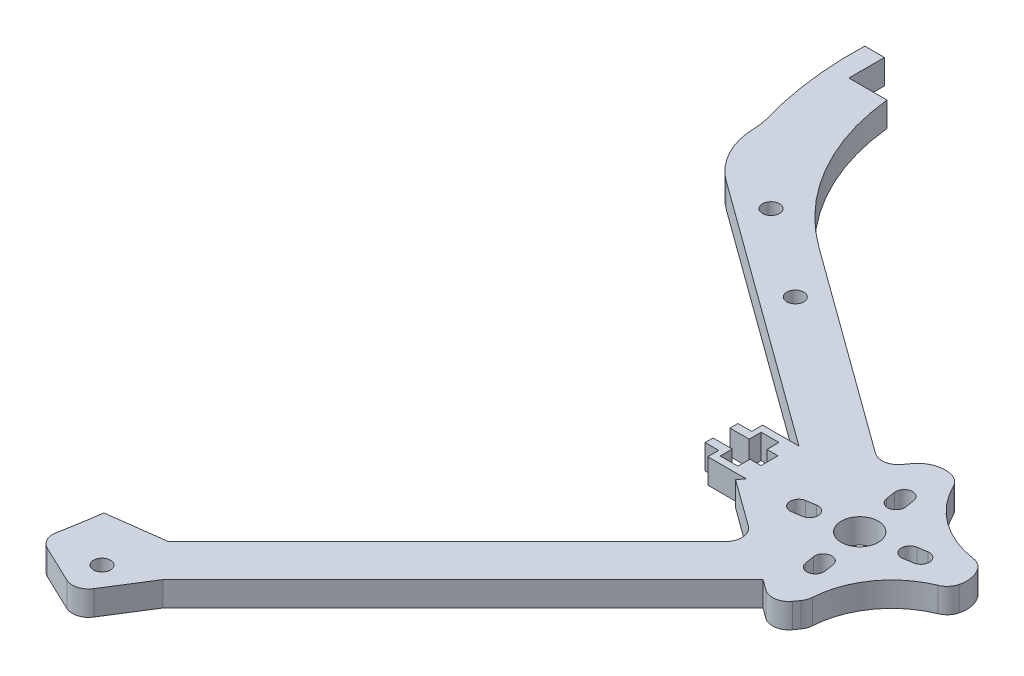
SolidWorks part; units mm, degrees
material "PPS"
ref_plane "前视基准面" through (0, 0, 0) normal (0, 0, 1) x (1, 0, 0)
ref_plane "上视基准面" through (0, 0, 0) normal (0, 1, 0) x (1, 0, 0)
ref_plane "右视基准面" through (0, 0, 0) normal (1, 0, 0) x (0, 0, -1)
sketch "草图3" plane through (0, 0, 0) normal (0, 1, 0) x (1, 0, 0)
  line L0 (0, 0) -> (35.4735, 0) construction
  line L1 (0, 0) -> (62.3757, -45.3186) construction
  line L2 (41.1319, -24.0128) -> (94.6944, -62.9282)
  line L3 (94.6944, -62.9282) -> (100.1314, -55.4448)
  line L4 (100.1314, -55.4448) -> (122.7839, -71.9028)
  line L5 (122.7839, -71.9028) -> (106.3259, -94.5552)
  line L6 (83.6734, -78.0972) -> (106.3259, -94.5552) construction
  line L9 (77.9994, -109.7251) -> (128.6275, -40.0415) construction
  line L11 (103.2286, -75) -> (90.242, -77.0569) construction
  line L13 (111.1302, -73.7485) -> (112.8586, -73.4748) construction
  line L14 (110.8877, -72.2176) -> (112.6161, -71.9438)
  line L15 (111.3726, -75.2794) -> (113.1011, -75.0057)
  line L16 (101.9772, -67.0985) -> (101.7034, -65.37) construction
  line L17 (103.5081, -66.856) -> (103.2343, -65.1276)
  line L18 (100.4463, -67.341) -> (100.1725, -65.6125)
  line L19 (95.3271, -76.2515) -> (93.5987, -76.5252) construction
  line L20 (95.5696, -77.7824) -> (93.8412, -78.0562)
  line L21 (95.0847, -74.7206) -> (93.3562, -74.9943)
  line L22 (104.4801, -82.9015) -> (104.7539, -84.63) construction
  line L23 (102.9492, -83.144) -> (103.223, -84.8724)
  line L24 (106.011, -82.659) -> (106.2848, -84.3875)
  line L25 (35.5479, -31.6984) -> (84.1364, -67)
  line L26 (84.1364, -67) -> (77.5, -67)
  line L27 (77.5, -67) -> (77.5, -69)
  line L28 (77.5, -69) -> (75, -69)
  line L29 (75, -69) -> (75, -70.45)
  line L30 (75, -70.45) -> (78.5, -70.45)
  line L31 (78.5, -70.45) -> (78.5, -68.25)
  line L32 (78.5, -68.25) -> (81.75, -68.25)
  line L33 (81.75, -68.25) -> (81.75, -70.45)
  line L34 (81.75, -70.45) -> (83.75, -70.45)
  line L35 (83.75, -70.45) -> (83.75, -73.55)
  line L36 (68.8077, -72) -> (90.242, -72) construction
  line L37 (81.75, -73.55) -> (83.75, -73.55)
  line L38 (81.75, -75.75) -> (81.75, -73.55)
  line L39 (78.5, -75.75) -> (81.75, -75.75)
  line L40 (78.5, -73.55) -> (78.5, -75.75)
  line L41 (75, -73.55) -> (78.5, -73.55)
  line L42 (75, -75) -> (75, -73.55)
  line L43 (77.5, -75) -> (75, -75)
  line L44 (77.5, -77) -> (77.5, -75)
  line L45 (84.1364, -77) -> (77.5, -77)
  line L47 (83.6734, -78.0972) -> (84.4706, -77)
  line L48 (84.4706, -77) -> (84.1364, -77)
  line L51 (41.6712, -139.6547) -> (94.9997, -86.3262)
  line L52 (94.9997, -86.3262) -> (83.6734, -78.0972)
  line L58 (47.1809, -146.1658) -> (101.962, -91.3847)
  line L61 (101.962, -91.3847) -> (106.3259, -94.5552)
  line L63 (31.6811, -151.7709) -> (40.8875, -156.1591)
  line L64 (47.1809, -146.1658) -> (40.8875, -156.1591)
  line L65 (41.6712, -139.6547) -> (31.2614, -141.0241)
  line L66 (42.309, -153.902) -> (47.6512, -145.4189) construction
  line L67 (31.6811, -151.7709) -> (38.4796, -155.0114) construction
  circle A5 centre (103.2286, -75) radius 3.375
  arc A6 (110.8877, -72.2176) -> (111.3726, -75.2794) centre (111.1302, -73.7485) ccw
  arc A7 (113.1011, -75.0057) -> (112.6161, -71.9438) centre (112.8586, -73.4748) ccw
  arc A8 (103.5081, -66.856) -> (100.4463, -67.341) centre (101.9772, -67.0985) cw
  arc A9 (100.1725, -65.6125) -> (103.2343, -65.1276) centre (101.7034, -65.37) cw
  arc A10 (95.5696, -77.7824) -> (95.0847, -74.7206) centre (95.3271, -76.2515) ccw
  arc A11 (93.3562, -74.9943) -> (93.8412, -78.0562) centre (93.5987, -76.5252) ccw
  arc A12 (102.9492, -83.144) -> (106.011, -82.659) centre (104.4801, -82.9015) cw
  arc A13 (106.2848, -84.3875) -> (103.223, -84.8724) centre (104.7539, -84.63) cw
  arc A16 (41.1319, -24.0128) -> (35.5479, -31.6984) centre (38.3399, -27.8556) ccw
  circle A17 centre (103.2286, -75) radius 66.25 construction
  circle A18 centre (44.0442, -32) radius 1.55
  circle A19 centre (60.2246, -43.7557) radius 1.55
  circle A28 centre (39.335, -149.4323) radius 1.55
  arc A29 (30.0249, -148.5011) -> (31.2329, -97.7907) centre (-122.0773, -119.5082) ccw construction
  arc A33 (31.2614, -141.0241) -> (30.0249, -148.5011) centre (-122.0773, -119.5082) cw
  arc A34 (30.0249, -148.5011) -> (31.6811, -151.7709) centre (32.9719, -149.0628) ccw construction
  arc A35 (30.0249, -148.5011) -> (31.6811, -151.7709) centre (32.9719, -149.0628) ccw
  point P11 (114.5549, -83.229)
  point P20 (111.9944, -73.6116)
  point P27 (101.8403, -66.2343)
  point P35 (94.4629, -76.3884)
  point P42 (104.617, -83.7657)
  point P54 (94.9997, -86.3262)
  point P67 (83.75, -72)
  dimension "D2" = 45
  dimension "D3" = 6.75
  dimension "D4" = 1.55
  dimension "D7" = 14
  dimension "D11" = 132.5
  dimension "D12" = 3.1
  dimension "D26" = 8.5
  dimension "D27" = 3.1
  dimension "D1" = 36
  dimension "D5" = 1.75
  dimension "D6" = 8
  dimension "D8" = 14
  dimension "D9" = 4.75
  dimension "D10" = 75
  dimension "D13" = 32
  dimension "D14" = 20
  dimension "D15" = 7.5
  dimension "D16" = 10
  dimension "D17" = 3.1
  dimension "D18" = 3.5
  dimension "D19" = 3.25
  dimension "D20" = 2
  dimension "D21" = 2.5
  dimension "D22" = 72
  dimension "D23" = 75
  dimension "D24" = 1.45
  dimension "D25" = 45
extrude "凸台-拉伸1" add sketch "草图3" along normal blind 4.5 contours L5 L4 L3 L2 A16 L25 L26 L27 L28 L29 L30 L31 L32 L33 L34 L35 L37 L38 L39 L40 L41 L42 L43 L44 L45 L48 L47 L52 L51 A19 A18 A11 L21 A10 L20 A7 L15 A6 L14 region at (66.9596, 0, 44.7829)
fillet "圆角-美观1" radius 5 2 edges at (100.1314, 2.25, 55.4448) (122.7839, 2.25, 71.9028)
sketch "草图4" plane through (0, 4.5, 0) normal (0, 1, 0) x (1, 0, 0)
  line L0 (104.1765, -58.3837) -> (118.7388, -68.9638)
  line L1 (119.8449, -75.9478) -> (109.2648, -90.5101)
  line L3 (103.2286, -75) -> (124.6569, -90.5685) construction
  line L4 (103.2286, -75) -> (89.033, -94.5387) construction
  line L5 (87.7185, -81.0362) -> (102.2808, -91.6163)
  line L7 (41.1319, -24.0128) -> (94.6944, -62.9282) construction
  arc A2 (102.2808, -91.6163) -> (87.7185, -81.0362) centre (86.1651, -98.4859) ccw
  arc A8 (118.7388, -68.9638) -> (104.1765, -58.3837) centre (120.2922, -51.5141) cw
  arc A9 (119.8449, -75.9478) -> (109.2648, -90.5101) centre (124.6569, -90.5685) ccw
extrude "圆弧-美观2" cut sketch "草图4" against normal up to next contours A8 L0 | L1 A9 region at (110.8688, 4.5, 64.4842) region at (113.6066, 4.5, 82.54)
fillet "圆角-美观3" radius 3 8 edges at (104.1765, 2.25, 58.3837) (118.7388, 2.25, 68.9638) (119.8449, 2.25, 75.9478) (94.6944, 2.25, 62.9282) (109.2648, 2.25, 90.5101) (94.9997, 2.25, 86.3262) (106.3259, 2.25, 94.5552) (40.8875, 2.25, 156.1591)
sketch "草图5" plane through (0, 0, 0) normal (0, 1, 0) x (1, 0, 0)
  line L0 (0, 0) -> (132.1913, 0) construction
  line L1 (0, 0) -> (0, 63.0505) construction
  line L2 (41.1319, -24.0128) -> (54.395, -33.649)
  line L3 (30.5, 2.25) -> (26.9026, 2.25)
  line L4 (30.5, 2.25) -> (30.5, -3.25)
  line L5 (30.5, -3.25) -> (30.5, -4.25)
  line L6 (30.5, -4.25) -> (37.4677, -4.25)
  line L7 (41.1319, -24.0128) -> (92.2673, -61.1648) construction
  line L8 (37.3772, -3.25) -> (30.5, -3.25) construction
  line L9 (30.5, -3.25) -> (30.5, 3.25) construction
  line L10 (30.5, 3.25) -> (26.9448, 3.25) construction
  line L11 (41.1319, -24.0128) -> (35.5479, -31.6984)
  line L13 (34.4971, -25.0636) -> (29.8517, -19.5014) construction
  arc A0 (34.4971, -25.0636) -> (41.1319, -24.0128) centre (38.3399, -27.8556) cw construction
  arc A1 (34.4971, -25.0636) -> (35.5479, -31.6984) centre (38.3399, -27.8556) ccw construction
  arc A2 (29.8211, -20.7007) -> (35.5479, -31.6984) centre (43.7171, -20.4546) ccw
  arc A3 (29.8211, -20.7007) -> (29.4289, -18.099) centre (19.8227, -20.8778) ccw
  arc A6 (26.9026, 2.25) -> (29.4289, -18.099) centre (91.9966, 0) ccw
  arc A7 (29.8202, 19.4008) -> (29.8202, -19.4008) centre (91.9966, 0) ccw construction
  arc A8 (54.395, -33.649) -> (37.3772, -3.25) centre (78.8424, 0) cw construction
  arc A9 (29.4289, -18.099) -> (26.9448, 3.25) centre (91.9966, 0) cw construction
  arc A12 (41.1319, -24.0128) -> (35.5479, -31.6984) centre (38.3399, -27.8556) ccw construction
  arc A14 (54.395, 33.649) -> (54.395, -33.649) centre (78.8424, 0) ccw construction
  arc A15 (37.4677, -4.25) -> (42.5499, -20.3171) centre (78.8424, 0) ccw
  arc A16 (54.395, -33.649) -> (42.5499, -20.3171) centre (78.8424, 0) cw
  dimension "D1" = 3.25
  dimension "D5" = 1
  dimension "D2" = 3.25
  dimension "D3" = 30.5
  dimension "D4" = 1
extrude "机臂配合防旋转" add sketch "草图5" along normal up to surface (4.5 mm away) up to face at (39.335, 4.5, 150.9823)
